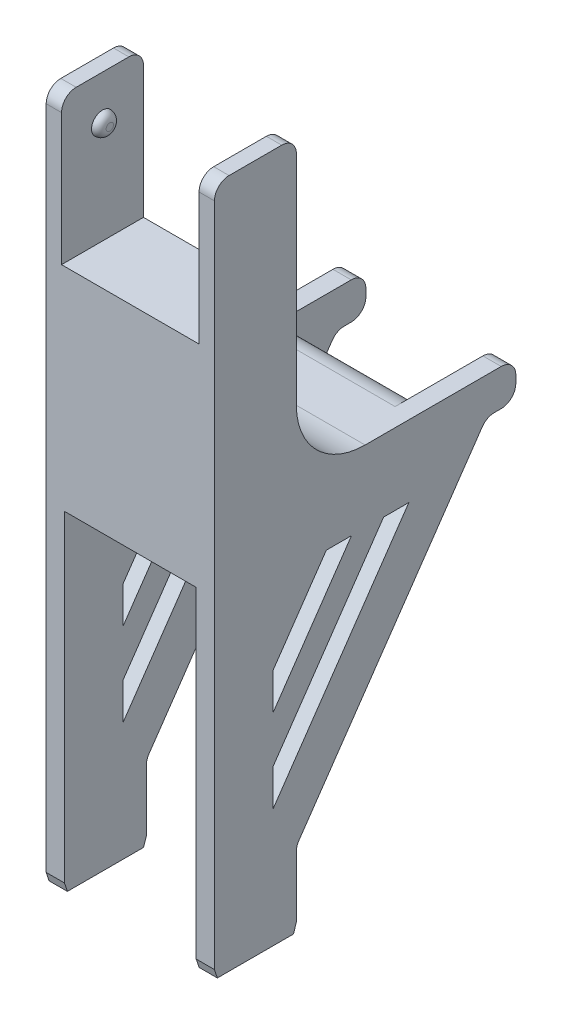
SolidWorks part; units mm, degrees
ref_plane "Front Plane" through (0, 0, 0) normal (0, 0, 1) x (1, 0, 0)
ref_plane "Top Plane" through (0, 0, 0) normal (0, 1, 0) x (1, 0, 0)
ref_plane "Right Plane" through (0, 0, 0) normal (1, 0, 0) x (0, 0, -1)
sketch "Szkic1" plane through (0, 0, 0) normal (1, 0, 0) x (0, 0, -1)
  line L2 (0, 0) -> (-10.3, 0)
  line L5 (-15, 4.7) -> (-15, 20.6)
  line L6 (-15, 20.6) -> (-20.6, 20.6)
  line L7 (-20.6, 20.6) -> (-20.6, -21.4)
  line L8 (0, 0) -> (0, -2.5)
  line L9 (0, -2.5) -> (-2, -2.5)
  line L10 (-2, -2.5) -> (-15, -21.4)
  line L11 (-15, -21.4) -> (-15, -25.9)
  line L13 (-20.6, -25.9) -> (-20.6, -21.4)
  line L16 (-20.6, -25.9) -> (-20.4, -26.5)
  line L17 (-20.4, -26.5) -> (-15.2, -26.5)
  line L18 (-15.2, -26.5) -> (-15, -25.9)
  arc A0 (-15, 4.7) -> (-10.3, 0) centre (-10.3, 4.7) ccw
  point P15 (-10.3, 4.7)
  dimension "D5" = 2.5
  dimension "D7" = 4.7
  dimension "D1" = 42
  dimension "D2" = 20.6
  dimension "D3" = 15.9
  dimension "D4" = 5.6
  dimension "D6" = 2
  dimension "D8" = 18.9
  dimension "D9" = 4.5
  dimension "D10" = 0.6
  dimension "D11" = 4.5
  dimension "D12" = 0.2
extrude "Dodanie-wyciągnięcie1" add sketch "Szkic1" along normal blind 11.5
ref_plane "Płaszczyzna dolna" through (0, 0, 20.6) normal (0, 0, 1) x (1, 0, 0)
sketch "Szkic2" plane through (0, 0, 20.6) normal (0, 0, 1) x (1, 0, 0)
  line L0 (5.75, 20.6) -> (5.75, -25.9) construction
  line L1 (11.5, 20.6) -> (0, 20.6) construction
  line L4 (10.45, 10.6) -> (1.05, 10.6)
  line L5 (10.45, 10.6) -> (10.45, 20.6)
  line L6 (10.45, 20.6) -> (1.05, 20.6)
  line L7 (1.05, 10.6) -> (1.05, 20.6)
  line L8 (10.45, 10.6) -> (1.05, 20.6) construction
  line L9 (10.45, 20.6) -> (1.05, 10.6) construction
  line L10 (10.25, -3.9) -> (1.25, -3.9)
  line L11 (10.25, -3.9) -> (10.25, -28.2703)
  line L12 (10.25, -28.2703) -> (1.25, -28.2703)
  line L13 (1.25, -3.9) -> (1.25, -28.2703)
  line L14 (10.25, -3.9) -> (1.25, -28.2703) construction
  line L15 (10.25, -28.2703) -> (1.25, -3.9) construction
  point P6 (5.75, 15.6)
  point P11 (5.75, -14.9)
  point P16 (0, 0)
  dimension "D1" = 9.4
  dimension "D2" = 10
  dimension "D3" = 9
  dimension "D4" = 11
extrude "Wytnij-wyciągnięcie1" cut sketch "Szkic2" against normal through all
ref_plane "Płaszczyzna boczna" through (11.5, 0, 0) normal (1, 0, 0) x (0, 0, -1)
sketch "Szkic3" plane through (11.5, 0, 0) normal (1, 0, 0) x (0, 0, -1)
  line L0 (-16.6, -12.7056) -> (-16.6, -10.1985)
  line L1 (-16.6, -10.1985) -> (-12.9555, -4.9)
  line L2 (-12.9555, -4.9) -> (-11.2311, -4.9)
  line L3 (-11.2311, -4.9) -> (-16.6, -12.7056)
  line L4 (-16.6, -15.8972) -> (-16.6, -18.4043)
  line L5 (-16.6, -18.4043) -> (-7.3113, -4.9)
  line L6 (-7.3113, -4.9) -> (-9.0358, -4.9)
  line L7 (-9.0358, -4.9) -> (-16.6, -15.8972)
  line L8 (-15, -21.4) -> (-2, -2.5) construction
  line L10 (-20.6, 6.325) -> (-20.6, -6.325) construction
  dimension "D1" = 4
  dimension "D2" = 21
extrude "Wytnij-wyciągnięcie2" cut sketch "Szkic3" against normal through all both and the other way through all
ref_plane "Płaszczyzna3" through (0, 0, 0) normal (0, 1, 0) x (1, 0, 0)
sketch "Szkic4" plane through (0, 0, 0) normal (0, 1, 0) x (1, 0, 0)
  line L0 (5.75, -5) -> (5.75, 0) construction
  line L2 (11.5, 0) -> (0, 0) construction
  line L4 (1.25, -5) -> (10.25, -5)
  line L5 (1.25, -5) -> (1.25, 0)
  line L6 (1.25, 0) -> (10.25, 0)
  line L7 (10.25, -5) -> (10.25, 0)
  line L8 (1.25, -5) -> (10.25, 0) construction
  line L9 (1.25, 0) -> (10.25, -5) construction
  point P6 (5.75, -2.5)
  dimension "D1" = 9
  dimension "D2" = 5
extrude "Wytnij-wyciągnięcie3" cut sketch "Szkic4" against normal blind 10
fillet "Zaokrąglenie1" radius 2 2 edges at (5.75, -3.9, 5) (5.75, 0, 5)
fillet "Zaokrąglenie2" radius 1 12 edges at (0.625, 0, 0) (0.625, -2.5, 0) (10.875, -2.5, 0) (10.875, 0, 0) (10.975, 20.6, 20.6) (10.975, 20.6, 15) (0.525, 20.6, 20.6) (0.525, 20.6, 15) (0.625, -2.5, 2) (10.875, -2.5, 2) (0.625, -21.4, 15) (10.875, -21.4, 15)
ref_plane "Płaszczyzna4" through (10.45, 0, 0) normal (-1, 0, 0) x (0, 0, 1)
sketch "Szkic5" plane through (10.45, 0, 0) normal (-1, 0, 0) x (0, 0, 1)
  line L3 (17.8, 20.6) -> (17.8, 10.6) construction
  line L4 (16, 20.6) -> (19.6, 20.6) construction
  line L5 (15, 10.6) -> (20.6, 10.6) construction
  circle A0 centre (17.8, 17.6) radius 0.75
  dimension "D1" = 1.5
  dimension "D2" = 3
extrude "Dodanie-wyciągnięcie2" add sketch "Szkic5" along normal blind 0.5
fillet "Zaokrąglenie3" radius 0.5 1 edges at (9.95, 16.85, 17.8)
ref_plane "Płaszczyzna5" through (5.75, 0, 0) normal (1, 0, 0) x (0, 0, -1)
mirror "Lustro2" about plane through (5.75, 0, 0) normal (1, 0, 0) of bodies 113 115
